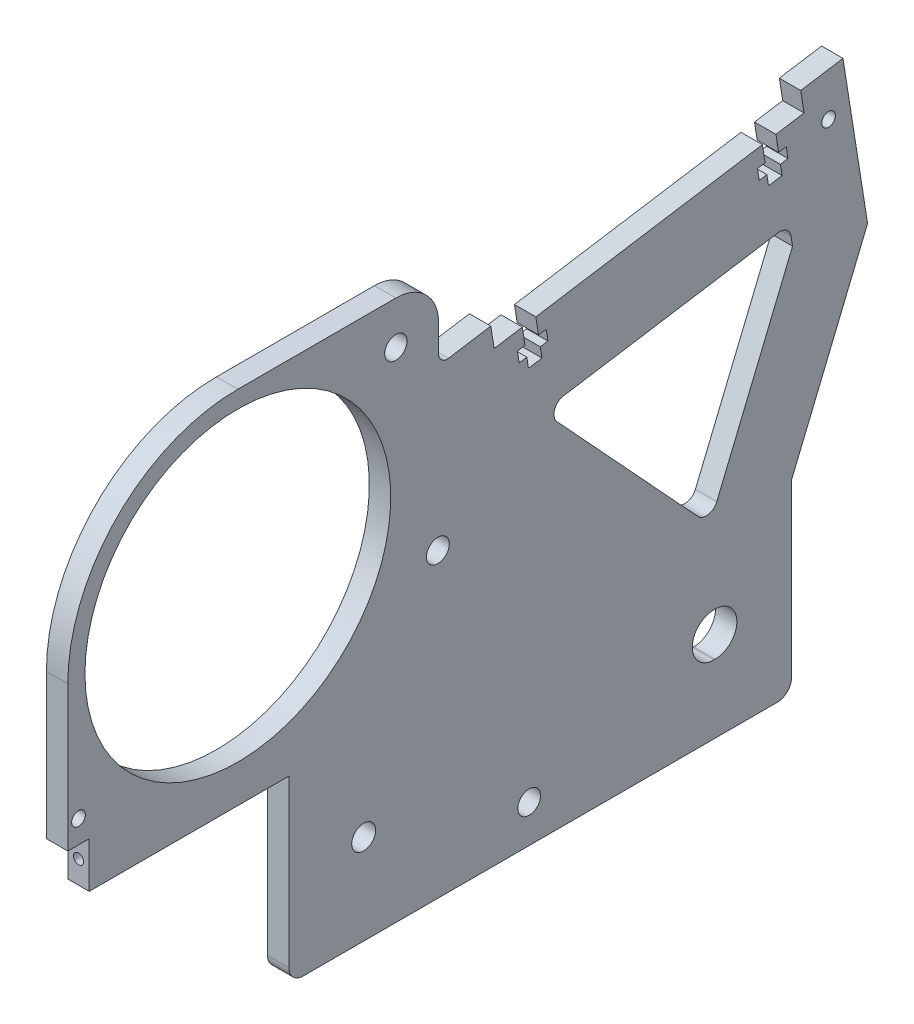
SolidWorks part; units mm, degrees
ref_plane "Front Plane" through (0, 0, 0) normal (0, 0, 1) x (1, 0, 0)
ref_plane "Top Plane" through (0, 0, 0) normal (0, 1, 0) x (1, 0, 0)
ref_plane "Right Plane" through (0, 0, 0) normal (1, 0, 0) x (0, 0, -1)
sketch "Sketch1" plane through (0, 0, 0) normal (1, 0, 0) x (0, 0, -1)
  line L0 (-28.1703, 0) -> (77.3828, 0)
  line L1 (80.5578, 3.175) -> (80.5578, 38.5047)
  line L2 (-80.5578, 82.55) -> (-80.5578, 50.292)
  line L3 (-7.5328, 120.4) -> (-42.7078, 120.4) construction
  line L4 (-75.7953, 50.292) -> (-75.7953, 40.132)
  line L5 (63.5398, 20.066) -> (63.2858, 20.066) construction
  line L6 (63.5398, 15.2273) -> (63.2858, 15.2273)
  line L7 (-75.7953, 40.132) -> (-31.3453, 40.132)
  line L8 (-7.5328, 120.4) -> (-42.7078, 120.4)
  line L9 (80.5578, 38.5047) -> (80.5578, 41.307)
  line L10 (-31.3453, 40.132) -> (-31.3453, 3.175)
  line L11 (-80.5578, 50.292) -> (-75.7953, 50.292)
  line L12 (63.5398, 24.9047) -> (63.2858, 24.9047)
  line L15 (77.5375, 90.432) -> (29.7985, 82.8709) construction
  line L16 (28.3297, 78.6391) -> (59.6993, 44.664) construction
  line L17 (63.9131, 45.4172) -> (80.7745, 86.2313) construction
  line L18 (80.7745, 86.2313) -> (80.4436, 88.3207) construction
  line L19 (77.5375, 90.432) -> (29.7985, 82.8709)
  line L20 (28.3297, 78.6391) -> (59.6993, 44.664)
  line L21 (63.9131, 45.4172) -> (80.7745, 86.2313)
  line L22 (80.7745, 86.2313) -> (80.4436, 88.3207)
  line L25 (80.5578, 41.307) -> (97.4765, 82.2596) construction
  line L26 (97.4765, 82.2596) -> (92.0007, 116.8321) construction
  line L27 (92.0007, 116.8321) -> (82.593, 115.3421) construction
  line L28 (82.593, 115.3421) -> (83.338, 110.6382) construction
  line L29 (83.338, 110.6382) -> (77.0662, 109.6449) construction
  line L30 (80.5578, 41.307) -> (97.4765, 82.2596)
  line L31 (97.4765, 82.2596) -> (92.0007, 116.8321)
  line L32 (92.0007, 116.8321) -> (82.593, 115.3421)
  line L33 (82.593, 115.3421) -> (83.338, 110.6382)
  line L34 (83.338, 110.6382) -> (77.0662, 109.6449)
  line L35 (77.0662, 109.6449) -> (77.6672, 105.8504) construction
  line L36 (74.6567, 105.3736) -> (74.0557, 109.168) construction
  line L37 (72.9633, 105.1054) -> (74.6567, 105.3736) construction
  line L38 (77.6672, 105.8504) -> (79.3605, 106.1186) construction
  line L39 (79.3605, 106.1186) -> (79.7529, 103.6412) construction
  line L40 (79.7529, 103.6412) -> (78.0595, 103.373) construction
  line L41 (73.3557, 102.628) -> (72.9633, 105.1054) construction
  line L42 (75.0491, 102.8962) -> (73.3557, 102.628) construction
  line L43 (75.4216, 100.5443) -> (75.0491, 102.8962) construction
  line L44 (78.432, 101.0211) -> (75.4216, 100.5443) construction
  line L45 (78.0595, 103.373) -> (78.432, 101.0211) construction
  line L46 (74.0557, 109.168) -> (23.6303, 101.1814) construction
  line L47 (77.0662, 109.6449) -> (77.6672, 105.8504)
  line L48 (74.6567, 105.3736) -> (74.0557, 109.168)
  line L49 (72.9633, 105.1054) -> (74.6567, 105.3736)
  line L50 (77.6672, 105.8504) -> (79.3605, 106.1186)
  line L51 (79.3605, 106.1186) -> (79.7529, 103.6412)
  line L52 (79.7529, 103.6412) -> (78.0595, 103.373)
  line L53 (73.3557, 102.628) -> (72.9633, 105.1054)
  line L54 (75.0491, 102.8962) -> (73.3557, 102.628)
  line L55 (75.4216, 100.5443) -> (75.0491, 102.8962)
  line L56 (78.432, 101.0211) -> (75.4216, 100.5443)
  line L57 (78.0595, 103.373) -> (78.432, 101.0211)
  line L58 (74.0557, 109.168) -> (23.6303, 101.1814)
  line L59 (23.6303, 101.1814) -> (24.2312, 97.387) construction
  line L60 (24.2312, 97.387) -> (25.9246, 97.6552) construction
  line L61 (25.9246, 97.6552) -> (26.317, 95.1778) construction
  line L62 (26.317, 95.1778) -> (24.6236, 94.9096) construction
  line L63 (24.6236, 94.9096) -> (24.9961, 92.5577) construction
  line L64 (24.9961, 92.5577) -> (21.9857, 92.0809) construction
  line L65 (21.9857, 92.0809) -> (21.6131, 94.4328) construction
  line L66 (21.6131, 94.4328) -> (19.9198, 94.1646) construction
  line L67 (19.9198, 94.1646) -> (19.5274, 96.642) construction
  line L68 (19.5274, 96.642) -> (21.2208, 96.9102) construction
  line L69 (21.2208, 96.9102) -> (20.6198, 100.7046) construction
  line L70 (20.6198, 100.7046) -> (14.348, 99.7113) construction
  line L71 (23.6303, 101.1814) -> (24.2312, 97.387)
  line L72 (24.2312, 97.387) -> (25.9246, 97.6552)
  line L73 (25.9246, 97.6552) -> (26.317, 95.1778)
  line L74 (26.317, 95.1778) -> (24.6236, 94.9096)
  line L75 (24.6236, 94.9096) -> (24.9961, 92.5577)
  line L76 (24.9961, 92.5577) -> (21.9857, 92.0809)
  line L77 (21.9857, 92.0809) -> (21.6131, 94.4328)
  line L78 (21.6131, 94.4328) -> (19.9198, 94.1646)
  line L79 (19.9198, 94.1646) -> (19.5274, 96.642)
  line L80 (19.5274, 96.642) -> (21.2208, 96.9102)
  line L81 (21.2208, 96.9102) -> (20.6198, 100.7046)
  line L82 (20.6198, 100.7046) -> (14.348, 99.7113)
  line L83 (14.348, 99.7113) -> (13.6029, 104.4151) construction
  line L84 (13.6029, 104.4151) -> (4.1952, 102.9251) construction
  line L85 (1.9922, 104.8066) -> (1.9922, 110.875) construction
  line L86 (14.348, 99.7113) -> (13.6029, 104.4151)
  line L87 (13.6029, 104.4151) -> (4.1952, 102.9251)
  line L88 (1.9922, 104.8066) -> (1.9922, 110.875)
  arc A0 (63.5398, 15.2273) -> (63.5398, 24.9047) centre (63.5398, 20.066) ccw
  circle A1 centre (-42.7078, 82.55) radius 31.5 construction
  circle A2 centre (63.5398, 20.066) radius 77.47 construction
  circle A3 centre (-78.1765, 55.372) radius 1.524
  arc A4 (63.2858, 24.9047) -> (63.2858, 15.2273) centre (63.2858, 20.066) ccw
  arc A5 (-42.7078, 120.4) -> (-80.5578, 82.55) centre (-42.7078, 82.55) ccw
  arc A6 (-28.1703, 0) -> (-31.3453, 3.175) centre (-28.1703, 3.175) cw
  arc A7 (77.3828, 0) -> (80.5578, 3.175) centre (77.3828, 3.175) ccw
  arc A10 (29.7985, 82.8709) -> (28.3297, 78.6391) centre (30.1958, 80.3622) ccw construction
  circle A11 centre (-14.6922, 20.066) radius 2.667
  arc A12 (59.6993, 44.664) -> (63.9131, 45.4172) centre (61.5655, 46.387) ccw construction
  arc A14 (80.4436, 88.3207) -> (77.5375, 90.432) centre (77.9349, 87.9233) ccw construction
  arc A15 (29.7985, 82.8709) -> (28.3297, 78.6391) centre (30.1958, 80.3622) ccw
  circle A16 centre (-42.7078, 82.55) radius 34.04
  arc A17 (59.6993, 44.664) -> (63.9131, 45.4172) centre (61.5655, 46.387) ccw
  circle A18 centre (22.1378, 8.382) radius 2.54
  arc A19 (80.4436, 88.3207) -> (77.5375, 90.432) centre (77.9349, 87.9233) ccw
  circle A20 centre (1.8178, 67.06) radius 2.54
  circle A23 centre (88.7869, 106.6794) radius 1.524 construction
  circle A25 centre (88.7869, 106.6794) radius 1.524
  arc A26 (1.9922, 104.8066) -> (4.1952, 102.9251) centre (3.8972, 104.8066) ccw construction
  arc A27 (1.9922, 110.875) -> (-7.5328, 120.4) centre (-7.5328, 110.875) ccw construction
  circle A28 centre (-7.5328, 110.875) radius 2.4892 construction
  arc A29 (1.9922, 104.8066) -> (4.1952, 102.9251) centre (3.8972, 104.8066) ccw
  arc A30 (1.9922, 110.875) -> (-7.5328, 120.4) centre (-7.5328, 110.875) ccw
  circle A31 centre (-7.5328, 110.875) radius 2.4892
  point P13 (63.4128, 20.066)
  dimension "D4" = 9.6774
  dimension "D7" = 4.7625
  dimension "D8" = 63
  dimension "D9" = 5.08
  dimension "D12" = 3.175
  dimension "D13" = 8.382
  dimension "D14" = 2.54
  dimension "D15" = 154.94
  dimension "D18" = 5.334
  dimension "D19" = 5.08
  dimension "D20" = 58.42
  dimension "D17" = 3.048
  dimension "D24" = 78.74
  dimension "D25" = 53.34
  dimension "D23" = 5.08
  dimension "D2" = 40.132
  dimension "D3" = 20.066
  dimension "D5" = 17.018
  dimension "D6" = 44.45
  dimension "D10" = 161.1156
  dimension "D11" = 95.25
  dimension "D21" = 0.254
  dimension "D22" = 10.16
  dimension "D16" = 2.3813
extrude "Boss-Extrude1" add sketch "Sketch1" along normal blind 4.7625
sketch "Sketch2" plane through (0, 0, 75.7953) normal (0, 0, 1) x (1, 0, 0)
  line L0 (0, 50.292) -> (0, 40.132) construction
  line L1 (4.7625, 40.132) -> (0, 40.132) construction
  circle A0 centre (2.3813, 45.212) radius 1.1303
  point P4 (0, 45.212)
  point P7 (2.3813, 40.132)
  dimension "D1" = 2.2606
extrude "Cut-Extrude1" cut sketch "Sketch2" against normal blind 6.35
